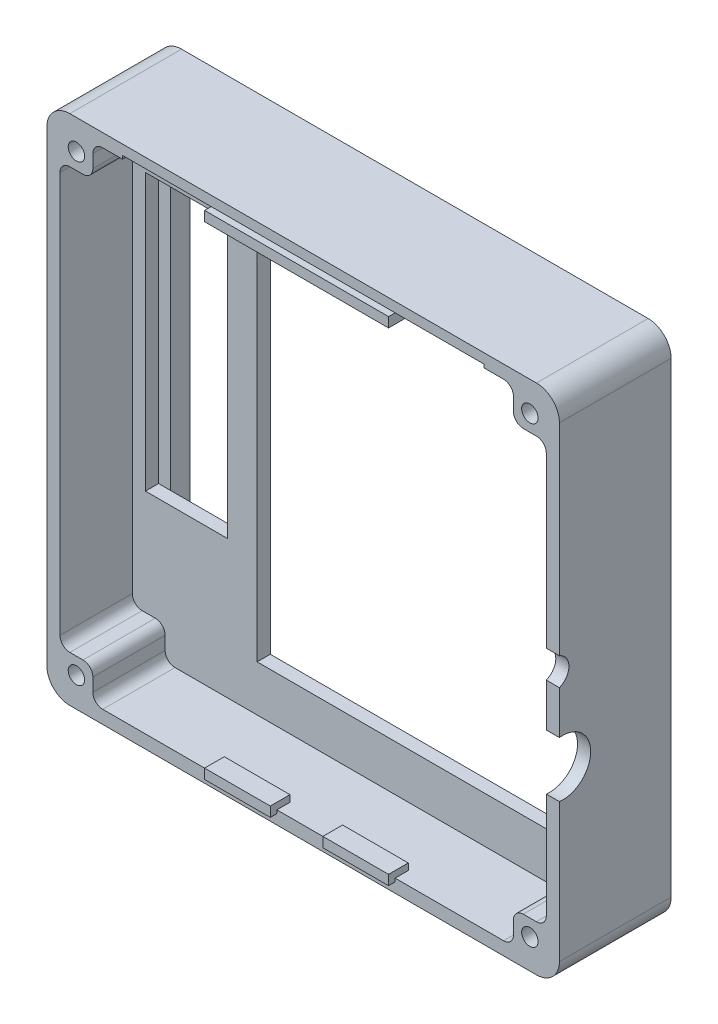
SolidWorks part; units mm, degrees
ref_plane "前视基准面" through (0, 0, 0) normal (0, 0, 1) x (1, 0, 0)
ref_plane "上视基准面" through (0, 0, 0) normal (0, 1, 0) x (1, 0, 0)
ref_plane "右视基准面" through (0, 0, 0) normal (1, 0, 0) x (0, 0, -1)
other "Configuration Table"
sketch "草图1" plane through (0, 0, 0) normal (0, 0, 1) x (1, 0, 0)
  line L1 (-39, -39) -> (39, -39)
  line L2 (-39, -39) -> (-39, 39)
  line L3 (-39, 39) -> (39, 39)
  line L4 (39, -39) -> (39, 39)
  line L5 (-39, -39) -> (39, 39) construction
  line L6 (-39, 39) -> (39, -39) construction
  point P0 (0, 0)
  dimension "D1" = 78
extrude "凸台-拉伸1" add sketch "草图1" along normal blind 6
sketch "草图2" plane through (0, 0, 6) normal (0, 0, 1) x (1, 0, 0)
  line L1 (-39, -39) -> (39, -39)
  line L2 (-39, -39) -> (-39, 39)
  line L3 (-39, 39) -> (39, 39)
  line L4 (39, -39) -> (39, 39)
  line L5 (-39, -39) -> (39, 39) construction
  line L6 (-39, 39) -> (39, -39) construction
  line L7 (37, 37) -> (-37, 37)
  line L8 (37, 37) -> (37, -37)
  line L9 (37, -37) -> (-37, -37)
  line L10 (-37, 37) -> (-37, -37)
  line L11 (37, 37) -> (-37, -37) construction
  line L12 (37, -37) -> (-37, 37) construction
  line L13 (-37, 37) -> (-32, 37)
  line L14 (-37, 37) -> (-37, 32)
  line L15 (-37, 32) -> (-32, 32)
  line L16 (-32, 37) -> (-32, 32)
  line L17 (37, 37) -> (32, 37)
  line L18 (37, 37) -> (37, 32)
  line L19 (37, 32) -> (32, 32)
  line L20 (32, 37) -> (32, 32)
  line L21 (-37, -37) -> (-32, -37)
  line L22 (-37, -37) -> (-37, -32)
  line L23 (-37, -32) -> (-32, -32)
  line L24 (-32, -37) -> (-32, -32)
  line L25 (37, -37) -> (32, -37)
  line L26 (37, -37) -> (37, -32)
  line L27 (37, -32) -> (32, -32)
  line L28 (32, -37) -> (32, -32)
  point P0 (0, 0)
  point P7 (0, 0)
  line M22 (39, -39) -> (39, 39)
  line M23 (39, 39) -> (-39, 39)
  line M24 (-39, 39) -> (-39, -39)
  line M25 (-39, -39) -> (39, -39)
  dimension "D1" = 2
  dimension "D2" = 5
extrude "凸台-拉伸2" add sketch "草图2" along normal blind 11 contours L10 L7 L8 L9 M25 M22 M23 M24 | L16 L7 L10 L15 | L7 L20 L19 L8 | L28 L9 L8 L27 | L9 L24 L23 L10 region at (-37.8969, 0, 6) region at (34.5, 34.5, 6) region at (-34.5, 34.5, 6) region at (34.5, -34.5, 6) region at (-34.5, -34.5, 6)
fillet "圆角1" radius 1.5 12 edges at (37, 32, 11.5) (32, 32, 11.5) (32, 37, 11.5) (37, -32, 11.5) (32, -32, 11.5) (32, -37, 11.5) (-32, -37, 11.5) (-32, -32, 11.5) (-37, -32, 11.5) (-37, 32, 11.5) (-32, 37, 11.5) (-32, 32, 11.5)
fillet "圆角2" radius 3.5 4 edges at (-39, 39, 8.5) (39, 39, 8.5) (39, -39, 8.5) (-39, -39, 8.5)
sketch "草图3" plane through (0, 0, 0) normal (0, 0, -1) x (-1, 0, 0)
  line L8 (37.5, -35.5) -> (37.5, 35.5)
  line L9 (-35.5, -37.5) -> (35.5, -37.5)
  line L10 (-37.5, 35.5) -> (-37.5, -35.5)
  line L11 (35.5, 37.5) -> (-35.5, 37.5)
  line L12 (37.5, -35.5) -> (37.5, 35.5)
  line L13 (-35.5, -37.5) -> (35.5, -37.5)
  line L14 (-37.5, 35.5) -> (-37.5, -35.5)
  line L15 (35.5, 37.5) -> (-35.5, 37.5)
  arc A8 (37.5, 35.5) -> (35.5, 37.5) centre (35.5, 35.5) ccw
  arc A9 (35.5, -37.5) -> (37.5, -35.5) centre (35.5, -35.5) ccw
  arc A10 (-37.5, -35.5) -> (-35.5, -37.5) centre (-35.5, -35.5) ccw
  arc A11 (-35.5, 37.5) -> (-37.5, 35.5) centre (-35.5, 35.5) ccw
  arc A12 (37.5, 35.5) -> (35.5, 37.5) centre (35.5, 35.5) ccw
  arc A13 (35.5, -37.5) -> (37.5, -35.5) centre (35.5, -35.5) ccw
  arc A14 (-37.5, -35.5) -> (-35.5, -37.5) centre (-35.5, -35.5) ccw
  arc A15 (-35.5, 37.5) -> (-37.5, 35.5) centre (-35.5, 35.5) ccw
  dimension "D1" = 1.5
extrude "切除-拉伸1" cut sketch "草图3" against normal blind 1
sketch "草图4" plane through (0, 0, 1) normal (0, 0, -1) x (-1, 0, 0)
  line L0 (35.5, 37.5) -> (-35.5, 37.5) construction
  line L1 (-33.2, 37.5) -> (33.2, 37.5)
  line L2 (-33.2, 37.5) -> (-33.2, -33.5)
  line L3 (-33.2, -33.5) -> (33.2, -33.5)
  line L4 (33.2, 37.5) -> (33.2, -33.5)
  line L6 (0, 0) -> (0, 26.6317) construction
  line L7 (-33.2, 37.1) -> (33.2, 37.1)
  line L8 (27.5, 37.1) -> (27.5, 37.5)
  line L9 (-27.5, 37.1) -> (-27.5, 37.5)
  line M10 (35.5, 37.5) -> (-35.5, 37.5)
  dimension "D1" = 71
  dimension "D2" = 66.4
  dimension "D3" = 0.4
  dimension "D4" = 55
extrude "切除-拉伸2" cut sketch "草图4" against normal blind 3 contours L3 L6 L7 L2 | L6 L3 L4 L7 | L7 L6 L9 M10 | L6 L7 L8 L1 region at (0, 37.3, 1) region at (30.35, 36.1308, 1)
sketch "草图5" plane through (0, 0, 1) normal (0, 0, -1) x (-1, 0, 0)
  line L0 (-35.5, 39) -> (35.5, 39) construction
  line L1 (-34.5, -34.5) -> (34.5, -34.5) construction
  line L2 (-34.5, -34.5) -> (-34.5, 34.5) construction
  line L3 (-34.5, 34.5) -> (34.5, 34.5) construction
  line L4 (34.5, -34.5) -> (34.5, 34.5) construction
  line L5 (-34.5, -34.5) -> (34.5, 34.5) construction
  line L6 (-34.5, 34.5) -> (34.5, -34.5) construction
  circle A0 centre (-34.5, 34.5) radius 1.25
  circle A1 centre (34.5, 34.5) radius 1.25
  circle A2 centre (34.5, -34.5) radius 1.25
  circle A3 centre (-34.5, -34.5) radius 1.25
  point P0 (0, 0)
  dimension "D2" = 2.5
  dimension "D1" = 4.5
extrude "切除-拉伸3" cut sketch "草图5" against normal through all
sketch "草图6" plane through (0, 0, 4) normal (0, 0, -1) x (-1, 0, 0)
  line L1 (-27.5, 37.5) -> (27.5, 37.5)
  line L2 (-27.5, 37.5) -> (-27.5, 35.5)
  line L3 (-27.5, 35.5) -> (27.5, 35.5)
  line L4 (27.5, 37.5) -> (27.5, 35.5)
  line L5 (-36, 28) -> (18, 28)
  line L6 (-36, 28) -> (-36, -30)
  line L7 (-36, -30) -> (18, -30)
  line L8 (18, 28) -> (18, -30)
  line L9 (22.5, 26) -> (35, 26)
  line L10 (22.5, 26) -> (22.5, -16)
  line L11 (22.5, -16) -> (35, -16)
  line L12 (35, 26) -> (35, -16)
  dimension "D1" = 2
  dimension "D2" = 54
  dimension "D3" = 30
  dimension "D4" = 58
  dimension "D5" = 36
  dimension "D6" = 22.5
  dimension "D7" = 12.5
  dimension "D8" = 42
  dimension "D9" = 16
extrude "切除-拉伸4" cut sketch "草图6" against normal through all
sketch "草图7" plane through (0, 0, 17) normal (0, 0, 1) x (1, 0, 0)
  line L0 (-15.0283, 0) -> (15.498, 0) construction
  line L17 (0, -8.9343) -> (0, 15.7561) construction
  line L20 (35.5, -37.5) -> (-35.5, -37.5) construction
  line L21 (14, -37.5) -> (4, -37.5)
  line L22 (14, -37.5) -> (14, -36)
  line L23 (14, -36) -> (4, -36)
  line L24 (4, -37.5) -> (4, -36)
  line L25 (-27.5, 37.5) -> (27.5, 37.5) construction
  line L26 (-4, -37.5) -> (-14, -37.5)
  line L27 (-4, -37.5) -> (-4, -36)
  line L28 (-4, -36) -> (-14, -36)
  line L29 (-14, -37.5) -> (-14, -36)
  line L30 (-14, 37.5) -> (14, 37.5)
  line L31 (-14, 37.5) -> (-14, 36)
  line L32 (-14, 36) -> (14, 36)
  line L33 (14, 37.5) -> (14, 36)
  dimension "D1" = 1.5
  dimension "D2" = 28
  dimension "D4" = 1.5
  dimension "D5" = 28
  dimension "D6" = 8
extrude "凸台-拉伸3" add sketch "草图7" along normal blind 1 and the other way blind 2
sketch "草图8" plane through (39, 0, 0) normal (1, 0, 0) x (0, 0, -1)
  line L0 (-17, -35.5) -> (0, -35.5) construction
  line L1 (-17, -35.5) -> (-17, 35.5) construction
  line L2 (-17, 4.8) -> (-17, 0.6) construction
  circle A0 centre (-16.5, -10.2) radius 4.25
  circle A1 centre (-17.8, 2.7) radius 2.2472
  dimension "D1" = 8.5
  dimension "D4" = 4.2
  dimension "D2" = 25.3
  dimension "D3" = 0.5
  dimension "D5" = 38.2
  dimension "D6" = 0.8
extrude "切除-拉伸5" cut sketch "草图8" against normal blind 10
sketch "草图9" plane through (0, -39, 0) normal (0, -1, 0) x (1, 0, 0)
  line L0 (-29, 14.5) -> (-17, 14.5) construction
  line L1 (-29, 15.5) -> (-17, 15.5)
  line L2 (-29, 13.5) -> (-17, 13.5)
  line L3 (-39, 0) -> (-39, 17) construction
  line L4 (-35.5, 17) -> (35.5, 17) construction
  line L5 (-29, 9.5) -> (-17, 9.5) construction
  line L6 (-29, 10.5) -> (-17, 10.5)
  line L7 (-29, 8.5) -> (-17, 8.5)
  line L8 (-29, 14.5) -> (-29, 9.5) construction
  line L9 (0, -1000) -> (0, 49000) construction
  line L11 (29, 9.5) -> (17, 9.5) construction
  line L12 (29, 10.5) -> (17, 10.5)
  line L13 (29, 8.5) -> (17, 8.5)
  line L14 (29, 14.5) -> (17, 14.5) construction
  line L15 (29, 15.5) -> (17, 15.5)
  line L16 (29, 13.5) -> (17, 13.5)
  arc A0 (-29, 15.5) -> (-29, 13.5) centre (-29, 14.5) ccw
  arc A1 (-17, 13.5) -> (-17, 15.5) centre (-17, 14.5) ccw
  arc A2 (-29, 10.5) -> (-29, 8.5) centre (-29, 9.5) ccw
  arc A3 (-17, 8.5) -> (-17, 10.5) centre (-17, 9.5) ccw
  arc A4 (29, 10.5) -> (29, 8.5) centre (29, 9.5) cw
  arc A5 (17, 8.5) -> (17, 10.5) centre (17, 9.5) cw
  arc A6 (29, 15.5) -> (29, 13.5) centre (29, 14.5) cw
  arc A7 (17, 13.5) -> (17, 15.5) centre (17, 14.5) cw
  point P2 (-23, 14.5)
  point P15 (-23, 9.5)
  point P27 (23, 9.5)
  point P34 (23, 14.5)
  dimension "D3" = 1
  dimension "D1" = 12
  dimension "D2" = 10
  dimension "D4" = 2.5
  dimension "D6" = 5
  dimension "D5" = 2
